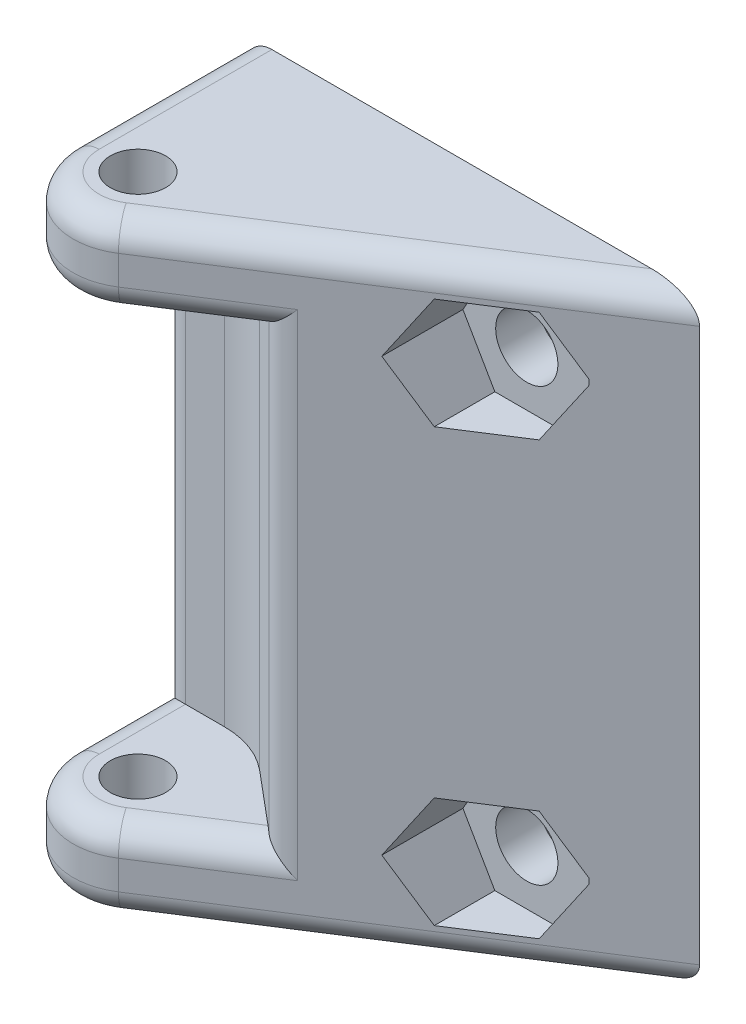
SolidWorks part; units mm, degrees
ref_plane "Front Plane" through (0, 0, 0) normal (0, 0, 1) x (1, 0, 0)
ref_plane "Top Plane" through (0, 0, 0) normal (0, 1, 0) x (1, 0, 0)
ref_plane "Right Plane" through (0, 0, 0) normal (1, 0, 0) x (0, 0, -1)
sketch "Sketch1" plane through (0, 0, 0) normal (0, 1, 0) x (1, 0, 0)
  line L2 (-4.7625, 12.7) -> (-4.7625, 0)
  line L3 (2.5745, -4.0067) -> (28.575, 12.7)
  line L4 (28.575, 12.7) -> (-4.7625, 12.7)
  circle A0 centre (0, 0) radius 2.032
  arc A1 (-4.7625, 0) -> (2.5745, -4.0067) centre (0, 0) ccw
  dimension "D1" = 4.064
  dimension "D2" = 28.575
  dimension "D4" = 4.7625
  dimension "D5" = 12.7
extrude "Boss-Extrude1" add sketch "Sketch1" along normal mid plane 44.45
sketch "Sketch6" plane through (0, 0, 0) normal (0, 1, 0) x (1, 0, 0)
  line L0 (0, 6.35) -> (-4.7625, 6.35)
  line L1 (-4.7625, 12.7) -> (-4.7625, 0) construction
  line L2 (-4.7625, 6.35) -> (-4.7625, 0)
  line L3 (4.0817, 4.8644) -> (9.4153, 0.3889)
  line L4 (2.5745, -4.0067) -> (28.575, 12.7) construction
  line L5 (9.4153, 0.3889) -> (2.5745, -4.0067)
  arc A0 (-4.7625, 0) -> (2.5745, -4.0067) centre (0, 0) ccw
  arc A2 (4.0817, 4.8644) -> (0, 6.35) centre (0, 0) ccw
  dimension "D1" = 6.35
  dimension "D2" = 140
extrude "Cut-Extrude4" cut sketch "Sketch6" against normal mid plane 32.5437
sketch "Sketch13" plane through (0, 0, -12.7) normal (0, 0, -1) x (-1, 0, 0)
  line L0 (-19.05, 15.875) -> (-19.05, -15.875) construction
  circle A0 centre (-19.05, 15.875) radius 2.286
  circle A1 centre (-19.05, -15.875) radius 2.286
  point P4 (-19.05, 0)
  dimension "D1" = 4.572
  dimension "D2" = 31.75
  dimension "D3" = 19.05
extrude "Cut-Extrude9" cut sketch "Sketch13" against normal through all
sketch "Sketch14" plane through (0, 0, -12.7) normal (0, 0, -1) x (-1, 0, 0)
  line L1 (-16.7036, 19.939) -> (-21.3964, 19.939)
  line L2 (-21.3964, 19.939) -> (-23.7427, 15.875)
  line L3 (-23.7427, 15.875) -> (-21.3964, 11.811)
  line L4 (-21.3964, 11.811) -> (-16.7036, 11.811)
  line L5 (-16.7036, 11.811) -> (-14.3573, 15.875)
  line L6 (-14.3573, 15.875) -> (-16.7036, 19.939)
  line L7 (-14.3573, -15.875) -> (-16.7036, -11.811)
  line L8 (-16.7036, -11.811) -> (-21.3964, -11.811)
  line L9 (-21.3964, -11.811) -> (-23.7427, -15.875)
  line L10 (-23.7427, -15.875) -> (-21.3964, -19.939)
  line L11 (-21.3964, -19.939) -> (-16.7036, -19.939)
  line L12 (-16.7036, -19.939) -> (-14.3573, -15.875)
  circle A0 centre (-19.05, 15.875) radius 4.064 construction
  circle A1 centre (-19.05, -15.875) radius 4.064 construction
  point P10 (0, 0)
  dimension "D1" = 8.128
  dimension "D2" = 8.128
extrude "Cut-Extrude10" cut sketch "Sketch14" against normal through all from offset 3.175 offset against normal yes
fillet "Fillet1" radius 1.905 14 edges at (-4.7625, -22.225, -6.35) (-2.2826, -22.225, 4.1799) (15.5747, 22.225, -4.3467) (-2.2826, 22.225, 4.1799) (15.5747, -22.225, -4.3467) (-4.7625, 22.225, -6.35) (-4.7625, -16.2719, -3.175) (5.9949, -16.2719, 1.8089) (-4.7625, 16.2719, -3.175) (-2.2826, 16.2719, 4.1799) (-2.2826, -16.2719, 4.1799) (5.9949, 16.2719, 1.8089) (-4.7625, 0, -6.35) (9.4153, 0, -0.3889)
